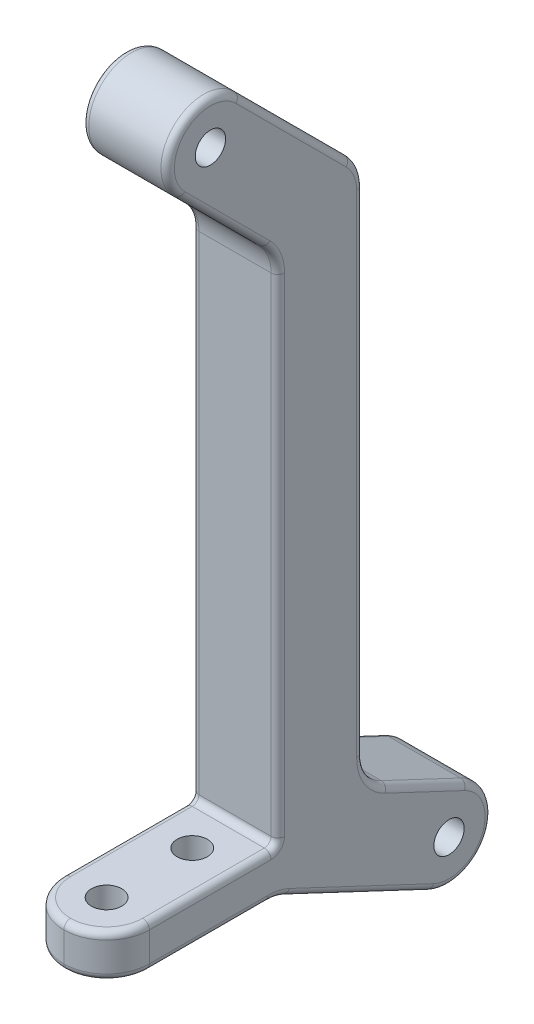
SolidWorks part; units mm, degrees
ref_plane "Front Plane" through (0, 0, 0) normal (0, 0, 1) x (1, 0, 0)
ref_plane "Top Plane" through (0, 0, 0) normal (0, 1, 0) x (1, 0, 0)
ref_plane "Right Plane" through (0, 0, 0) normal (1, 0, 0) x (0, 0, -1)
sketch "Sketch1" plane through (0, 0, 0) normal (1, 0, 0) x (0, 0, -1)
  line L0 (-25.4, 11.3) -> (-50.8, 11.3)
  line L1 (-50.8, 11.3) -> (-50.8, 4.95)
  line L2 (-50.8, 4.95) -> (-25.4, 4.95)
  line L3 (-12.7, 13.0047) -> (2.7069, 5.7441)
  line L4 (-25.4, 4.95) -> (-2.7069, -5.7441)
  line L6 (-25.4, 11.3) -> (-25.4, 87.3197)
  line L7 (-25.4, 87.3197) -> (-39.8901, 101.8099)
  line L8 (-30.9099, 110.7901) -> (-12.7, 92.5803)
  line L9 (-12.7, 92.5803) -> (-12.7, 13.0047)
  circle A0 centre (0, 0) radius 2.25
  circle A2 centre (-35.4, 106.3) radius 2.25
  circle A3 centre (-35.4, 106.3) radius 6.35
  circle A4 centre (0, 0) radius 6.35
  point P17 (0, 0)
  point P19 (-12.7, 11.3)
  dimension "D1" = 4.5
  dimension "D3" = 6.35
  dimension "D6" = 12.7
  dimension "D8" = 4.5
  dimension "D10" = 12.7
  dimension "D7" = 12.7
  dimension "D2" = 11.3
  dimension "D4" = 25.4
  dimension "D5" = 25.4
  dimension "D9" = 95
  dimension "D11" = 10
  dimension "D12" = 135
extrude "Boss-Extrude1" add sketch "Sketch1" along normal blind 12.7 contours A3 L7 L6 L0 L1 L2 L9 L8 A0 | A3 A2 | A4 A0 region at (0, 46.4533, 20.9695) region at (0, 110.6631, 39.7631) region at (0, 2.6304, 5.5817)
fillet "Fillet1" radius 6.35 4 edges at (6.35, 92.5803, 12.7) (6.35, 87.3197, 25.4) (6.35, 4.95, 25.4) (6.35, 13.0047, 12.7)
fillet "Fillet3" radius 6.35 2 edges at (0, 8.125, 50.8) (12.7, 8.125, 50.8)
fillet "Fillet4" radius 1 33 edges at (10.8401, 11.3, 48.9401) (1.8599, 11.3, 48.9401) (12.7, 11.3, 34.925) (0, 11.3, 34.925) (12.7, 47.9947, 25.4) (0, 47.9947, 25.4) (12.7, 87.1195, 25.8834) (0, 87.1195, 25.8834) (12.7, 95.4947, 33.575) (0, 95.4947, 33.575) (12.7, 110.7901, 39.8901) (0, 110.7901, 39.8901) (12.7, 102.6151, 22.7349) (0, 102.6151, 22.7349) (12.7, 92.38, 13.1834) (0, 92.38, 13.1834) (12.7, 53.491, 12.7) (0, 53.491, 12.7) (12.7, 4.95, 35.6356) (10.8401, 4.95, 48.9401) (1.8599, 4.95, 48.9401) (0, 4.95, 35.6356) (6.35, 11.3, 25.4) (12.7, 13.631, 11.7124) (12.7, 8.516, 3.175) (12.7, -2.7069, -5.7441) (12.7, -0.7, 13.4106) (12.7, 4.7967, 25.4343) (0, 13.631, 11.7124) (0, 8.516, 3.175) (0, -2.7069, -5.7441) (0, -0.7, 13.4106) (0, 4.7967, 25.4343)
sketch "Sketch2" plane through (0, 4.95, 0) normal (0, -1, 0) x (1, 0, 0)
  line L1 (0, 26.8213) -> (0, 44.45) construction
  circle A0 centre (6.35, 31.75) radius 2.25
  circle A1 centre (6.35, 44.45) radius 2.25
  dimension "D1" = 4.5
  dimension "D2" = 12.7
  dimension "D3" = 31.75
  dimension "D4" = 6.35
extrude "Cut-Extrude1" cut sketch "Sketch2" against normal up to next
